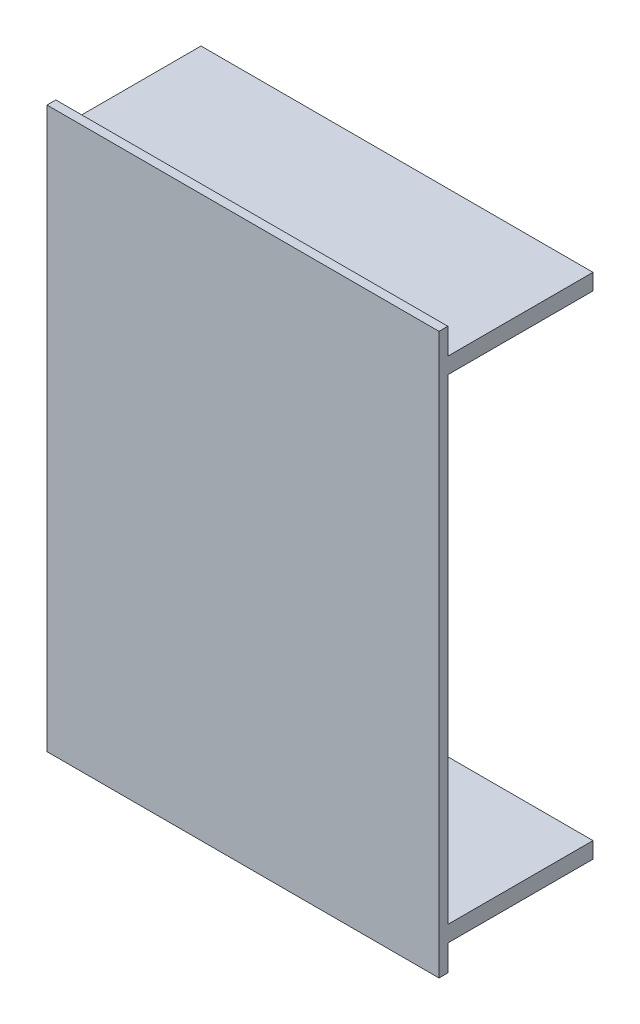
SolidWorks part; units mm, degrees
ref_plane "Front Plane" through (0, 0, 0) normal (0, 0, 1) x (1, 0, 0)
ref_plane "Top Plane" through (0, 0, 0) normal (0, 1, 0) x (1, 0, 0)
ref_plane "Right Plane" through (0, 0, 0) normal (1, 0, 0) x (0, 0, -1)
sketch "Sketch1" plane through (0, 0, 0) normal (0, 0, 1) x (1, 0, 0)
  line L1 (0, 0) -> (280, 0)
  line L2 (0, 0) -> (0, 400)
  line L3 (0, 400) -> (280, 400)
  line L4 (280, 0) -> (280, 400)
  dimension "D1" = 280
  dimension "D2" = 400
extrude "Boss-Extrude1" add sketch "Sketch1" along normal blind 6.3
sketch "Sketch4" plane through (0, 0, 0) normal (1, 0, 0) x (0, 0, -1)
  line L0 (0, 0) -> (0, 400) construction
  line L1 (0, 18.5) -> (103.7, 18.5)
  line L2 (0, 18.5) -> (0, 30)
  line L3 (0, 30) -> (103.7, 30)
  line L4 (103.7, 18.5) -> (103.7, 30)
  line L5 (-6.3, 200) -> (0, 200) construction
  line L6 (-6.3, 0) -> (-6.3, 400) construction
  line L7 (0, 370) -> (103.7, 370)
  line L8 (103.7, 381.5) -> (103.7, 370)
  line L9 (0, 381.5) -> (103.7, 381.5)
  line L10 (0, 381.5) -> (0, 370)
  dimension "D1" = 11.5
  dimension "D2" = 110
  dimension "D3" = 340
extrude "Boss-Extrude2" add sketch "Sketch4" along normal up to surface (280 mm away) up to face at (280, 200, 3.15)
ref_plane "Plane1" through (0, 0, -103.7) normal (0, 0, -1) x (-1, 0, 0)
ref_plane "Plane2" through (0, 200, 0) normal (0, 1, 0) x (1, 0, 0)
ref_plane "Plane3" through (140, 0, 0) normal (1, 0, 0) x (0, 0, -1)
